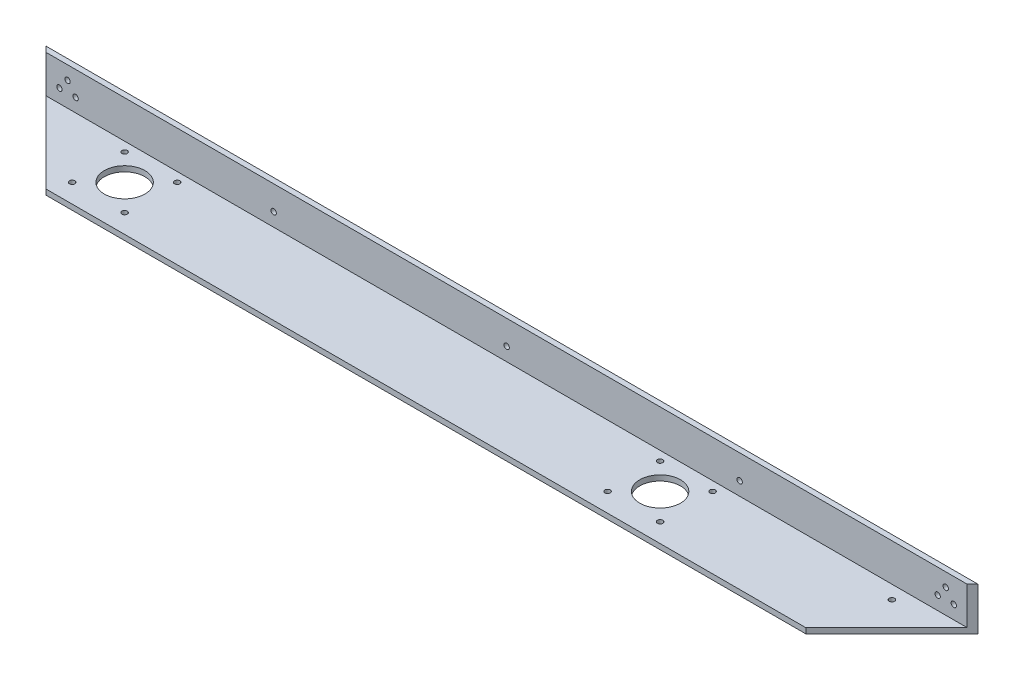
SolidWorks part; units mm, degrees
ref_plane "Front Plane" through (0, 0, 0) normal (0, 0, 1) x (1, 0, 0)
ref_plane "Top Plane" through (0, 0, 0) normal (0, 1, 0) x (1, 0, 0)
ref_plane "Right Plane" through (0, 0, 0) normal (1, 0, 0) x (0, 0, -1)
sketch "Sketch1" plane through (0, 0, 0) normal (1, 0, 0) x (0, 0, -1)
  line L0 (0, 0) -> (-50.8, 0)
  line L1 (-50.8, 0) -> (-50.8, 3.175)
  line L2 (-50.8, 3.175) -> (-3.175, 3.175)
  line L3 (-3.175, 3.175) -> (-3.175, 25.4)
  line L4 (-3.175, 25.4) -> (0, 25.4)
  line L5 (0, 25.4) -> (0, 0)
  dimension "LHeight" = 25.4
  dimension "LWidth" = 50.8
  dimension "LMaterialThickness" = 3.175
  dimension "D1" = 47.625
  dimension "D2" = 22.225
  dimension "D3" = 3.175
extrude "Boss-Extrude1" add sketch "Sketch1" along normal blind 550
chamfer "Chamfer7" distance 50.8 angle 45 1 edges at (0, 1.5875, 50.8)
chamfer "Chamfer8" distance 50.8 angle 45 1 edges at (550, 1.5875, 50.8)
sketch "BotthomHoles-Sketch2" plane through (0, 3.175, 0) normal (0, 1, 0) x (1, 0, 0)
  line L0 (546.825, -3.175) -> (3.175, -3.175) construction
  circle A0 centre (70.575, -24.175) radius 12
  circle A1 centre (386.575, -24.175) radius 12
  circle A2 centre (55.075, -8.675) radius 1.5875
  circle A3 centre (86.075, -8.675) radius 1.5875
  circle A4 centre (371.075, -8.675) radius 1.5875
  circle A5 centre (402.075, -8.675) radius 1.5875
  circle A6 centre (55.075, -39.675) radius 1.5875
  circle A7 centre (86.075, -39.675) radius 1.5875
  circle A8 centre (371.075, -39.675) radius 1.5875
  circle A9 centre (402.075, -39.675) radius 1.5875
  circle A11 centre (510.3125, -11.1125) radius 1.5875
  dimension "D9" = 3.175
  dimension "D10" = 24
  dimension "D2" = 8.675
  dimension "D3" = 31
  dimension "D4" = 15.5
  dimension "D5" = 15.5
  dimension "D6" = 31
  dimension "D7" = 15.5
  dimension "D8" = 31
  dimension "D11" = 21
  dimension "D12" = 316
  dimension "D13" = 70.575
  dimension "D17" = 39.6875
extrude "BottomHoles-Cut-Extrude1" cut sketch "BotthomHoles-Sketch2" against normal through all
sketch "LeftSideHoles-Sketch3" plane through (0, 0, 0) normal (0, 0, -1) x (-1, 0, 0)
  line L0 (0, 0) -> (0, 25.4) construction
  line L1 (-550, 0) -> (-550, 25.4) construction
  line L2 (-550, 25.4) -> (0, 25.4) construction
  circle A1 centre (-534.125, 17.4625) radius 1.5875
  circle A2 centre (-538.8875, 11.1125) radius 1.5875
  circle A3 centre (-529.3625, 11.1125) radius 1.5875
  circle A4 centre (-11.1125, 11.1125) radius 1.5875
  circle A5 centre (-20.6375, 11.1125) radius 1.5875
  circle A6 centre (-15.875, 17.4625) radius 1.5875
  circle A8 centre (-412.5, 11.1125) radius 1.5875
  circle A9 centre (-275, 11.1125) radius 1.5875
  circle A10 centre (-137.5, 11.1125) radius 1.5875
  dimension "D7" = 3.175
  dimension "D2" = 15.875
  dimension "D4" = 11.1125
  dimension "D6" = 15.875
  dimension "D8" = 137.5
  dimension "D9" = 137.5
  dimension "D10" = 137.5
  dimension "D5" = 11.1125
  dimension "D11" = 11.1125
  dimension "D3" = 7.9375
  dimension "D12" = 20.6375
  dimension "D13" = 20.6375
extrude "LeftSideHoles-Cut-Extrude2" cut sketch "LeftSideHoles-Sketch3" against normal through all
equation "\"LowerRailWidth\"= 2.00in"
equation "\"LowerRailHeight\"= 1.00in"
equation "\"RailThickness\"= .125in'Spec"
equation "\"SideRailHoleY1FromEdge\"= \"HoleOffsetFromEdge\""
equation "\"SideRailHoleX1FromSide\"= \"HoleOffsetFromSide\""
equation "\"StepperHoleDiameter\"= 24mm"
equation "\"StepperMountingHoleDiameter\"= 3.175mm"
equation "\"SideRailLength\"= 550mm"
equation "\"StepperMountingHoleDistance\"= 31mm'Spec"
equation "\"VSWidth\"= 1.25in'Spec"
equation "\"StepperMountingHoleOffsetFromLeftOrRightSide\"= \"StepperMountingHoleOffsetFromItsSide\" + \"RailThickness\""
equation "\"HoleOffsetFromEdge\"= \"RailThickness\" * 2.5"
equation "\"HoleOffsetFromSide\"= \"RailThickness\" * 3.5"
equation "\"StepperMountingHoleOffsetFromItsSide\"= 5.5mm'Spec"
equation "\"SideRailHoleX2FromSide\"= \"VSWidth\" - \"HoleOffsetFromEdge\" - \"RailThickness\"'Equals 20.6375"
equation "\"FasteningHoleDiameter\"= .125in"
equation "\"SideRailHoleY2FromSide\"= \"HoleOffsetFromSide\""
equation "\"LHeight@Sketch1\"=\"LowerRailHeight\""
equation "\"LWidth@Sketch1\"=\"LowerRailWidth\""
equation "\"D1@Chamfer7\"=\"LowerRailWidth\""
equation "\"D1@Chamfer8\"=\"LowerRailWidth\""
equation "\"D2@BotthomHoles-Sketch2\" = \"StepperMountingHoleOffsetFromLeftOrRightSide\""
equation "\"D3@BotthomHoles-Sketch2\" = \"StepperMountingHoleDistance\""
equation "\"D4@BotthomHoles-Sketch2\" = \"StepperMountingHoleDistance\" / 2"
equation "\"D5@BotthomHoles-Sketch2\"= \"StepperMountingHoleDistance\" / 2"
equation "\"D6@BotthomHoles-Sketch2\" = \"StepperMountingHoleDistance\""
equation "\"D7@BotthomHoles-Sketch2\" = \"StepperMountingHoleDistance\" / 2"
equation "\"D8@BotthomHoles-Sketch2\" = \"StepperMountingHoleDistance\""
equation "\"D9@BotthomHoles-Sketch2\" = \"StepperMountingHoleDiameter\""
equation "\"D10@BotthomHoles-Sketch2\" = \"StepperHoleDiameter\""
equation "\"D2@LeftSideHoles-Sketch3\"=\"VSMidSideRailHoleXFromSideToCenter\" - \"RailThickness\""
equation "\"D4@LeftSideHoles-Sketch3\" = \"SideRailHoleY2FromSide\""
equation "\"D7@LeftSideHoles-Sketch3\" = \"FasteningHoleDiameter\""
equation "\"D1@Boss-Extrude1\"=\"SideRailLength\""
equation "\"D6@LeftSideHoles-Sketch3\"=\"VSMidSideRailHoleXFromSideToCenter\" - \"RailThickness\""
equation "\"DistanceBetweenFrontToBackStepperHoles\"= \"BedLength\" - \"DistanceFromBedFrontToFirstLeftStepperHole\"'Equals 316"
equation "\"BedThirdSize\"= 70mm"
equation "\"BedLWidth\"= \"BedThirdSize\"'Equals 70"
equation "\"BedInnerSquareWidth\"= \"BedThirdSize\" * 3'Equals 210"
equation "\"BedInnerSquareLength\"= \"BedInnerSquareWidth\""
equation "\"BedLength\"= \"BedInnerSquareLength\" + \"BedLWidth\" * 2 + \"BedIncreasedByLength\"'Equals 350"
equation "\"D12@BotthomHoles-Sketch2\"=\"DistanceBetweenFrontToBackStepperHoles\""
equation "\"DistanceFromFrontSideToFirstLeftStepperHole\"= \"DistanceFromFrontSideToBedFront\" + \"DistanceFromBedFrontToFirstLeftStepperHole\"'Equals 70.575"
equation "\"D13@BotthomHoles-Sketch2\"=\"DistanceFromFrontSideToFirstLeftStepperHole\""
equation "\"DistanceFromBedFrontToFirstLeftStepperHole\"= \"LeadScrewNutPadSize\" + 10mm'Equals 34"
equation "\"DistanceFromFrontSideToBedFront\"= \"RailThickness\" + \"BeltTensionerDepth\" + 10mm'Equals 36.575"
equation "\"BeltTensionerDepth\"= \"BeltTensionerBackWallThickness\" + \"BeltTensionerInnerDepth\"'Equals 23.4"
equation "\"BeltTensionerBackWallThickness\"= 4mm"
equation "\"20TGT2PulleyDiameter\"= 17.9mm'Spec"
equation "\"BeltTensionerSpaceBetweenPulleyAndWall\"= 1.5mm"
equation "\"BeltTensionerInnerDepth\"= \"20TGT2PulleyDiameter\" + \"BeltTensionerSpaceBetweenPulleyAndWall\""
equation "\"BedIncreasedByLength\"= 0mm"
equation "\"LowerCornerBlockWidth\"= \"LowerRailWidth\" - \"RailThickness\" * 2'Room for left front stepper"
equation "\"D17@BotthomHoles-Sketch2\"=\"CornerEnclosureOffset\""
equation "\"CornerEnclosureOffset\"= \"LowerCornerBlockWidth\" - \"HoleOffsetFromEdge\" + \"RailThickness\""
equation "\"LeadScrewNutMountingHoleFlangeDiameter\"= 22mm'Spec"
equation "\"LeadScrewNutPadSize\"= \"LeadScrewNutMountingHoleFlangeDiameter\" + 2mm'Equals 24"
equation "\"LeftOrRightEnclosureOffsets\"= \"SideRailLength\" / 4"
equation "\"D8@LeftSideHoles-Sketch3\"=\"LeftOrRightEnclosureOffsets\""
equation "\"D9@LeftSideHoles-Sketch3\"=\"LeftOrRightEnclosureOffsets\""
equation "\"D10@LeftSideHoles-Sketch3\"=\"LeftOrRightEnclosureOffsets\""
equation "\"D5@LeftSideHoles-Sketch3\"=\"SideRailHoleX1FromSide\""
equation "\"D11@LeftSideHoles-Sketch3\"=\"SideRailHoleX1FromSide\""
equation "\"D3@LeftSideHoles-Sketch3\"=\"SideRailHoleY1FromEdge\""
equation "\"VSMidSideRailHoleXFromSideToCenter\"= \"RailThickness\" * 6"
equation "\"D12@LeftSideHoles-Sketch3\"=\"SideRailHoleX2FromSide\""
equation "\"D13@LeftSideHoles-Sketch3\"=\"SideRailHoleX2FromSide\""
